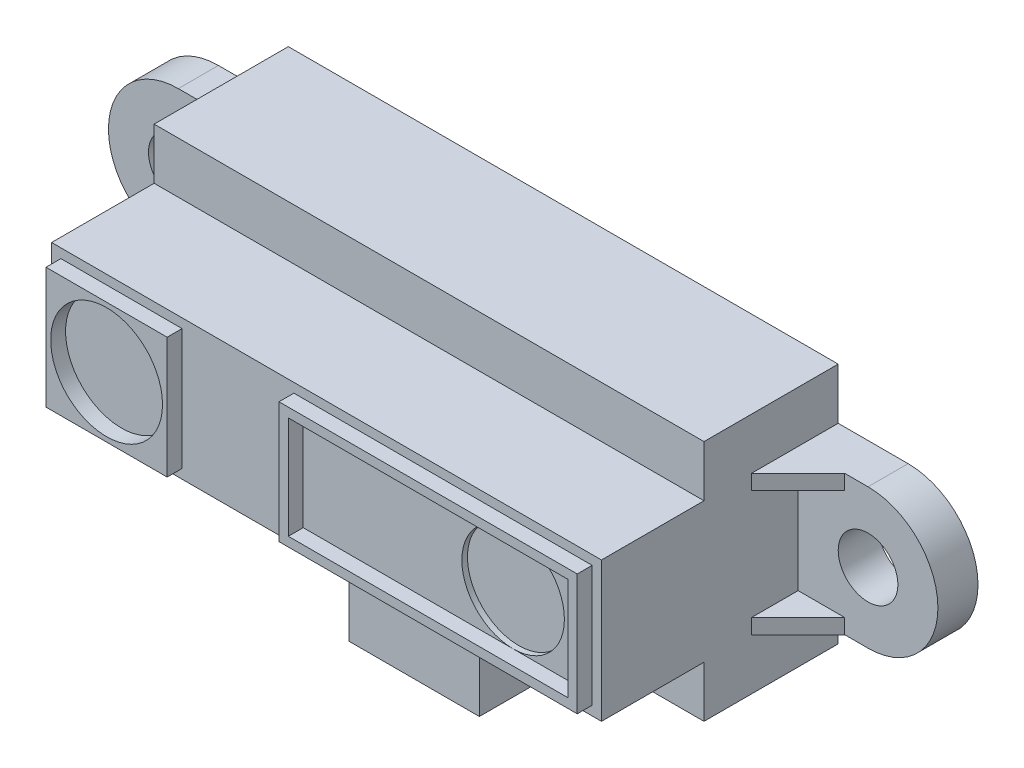
SolidWorks part; units mm, degrees
ref_plane "前视基准面" through (0, 0, 0) normal (0, 0, 1) x (1, 0, 0)
ref_plane "上视基准面" through (0, 0, 0) normal (0, 1, 0) x (1, 0, 0)
ref_plane "右视基准面" through (0, 0, 0) normal (1, 0, 0) x (0, 0, -1)
sketch "草图1" plane through (0, 0, 0) normal (0, 0, 1) x (1, 0, 0)
  line L0 (0, 0) -> (0, 16.7492) construction
  line L1 (-14.75, -3.75) -> (14.75, -3.75)
  line L2 (-14.75, -3.75) -> (-14.75, 3.75)
  line L3 (-14.75, 3.75) -> (14.75, 3.75)
  line L4 (14.75, -3.75) -> (14.75, 3.75)
  line L5 (-14.75, -3.75) -> (14.75, 3.75) construction
  line L6 (-14.75, 3.75) -> (14.75, -3.75) construction
  line L7 (-14.75, -3.75) -> (-18.5, -3.75)
  line L8 (14.75, -3.75) -> (18.5, -3.75)
  line L9 (14.75, 3.75) -> (18.5, 3.75)
  line L10 (-14.75, 3.75) -> (-18.5, 3.75)
  circle A0 centre (-18.5, 0) radius 3.75
  circle A1 centre (18.5, 0) radius 3.75
  circle A2 centre (-18.5, 0) radius 1.6
  circle A3 centre (18.5, 0) radius 1.6
  point P0 (0, 0)
  dimension "D3" = 37
  dimension "D4" = 3.2
  dimension "D5" = 3.2
  dimension "D1" = 29.5
  dimension "D2" = 7.5
extrude "凸台-拉伸1" add sketch "草图1" along normal blind 13.5 contours L1 L4 L3 L2 region at (0, 0, 0)
extrude "凸台-拉伸2" add sketch "草图1<4>" along normal blind 2.15 contours A0 A2 | A0 L2 L10 | A0 L7 L2 | L8 A1 L4 | A1 A3 | L4 A1 L9 region at (-15.5876, -2.9124, 0) region at (15.5876, -2.9124, 0) region at (-15.5876, 2.9124, 0) region at (-15.9233, -2.5767, 0) region at (15.5876, 2.9124, 0) region at (15.9233, 2.5767, 0)
sketch "草图1<4>" plane through (0, 0, 0) normal (0, 0, 1) x (1, 0, 0) same geometry as "草图1"
sketch "草图2" plane through (0, -3.75, 0) normal (0, -1, 0) x (1, 0, 0)
  line L0 (-14.75, 4.65) -> (-17.25, 2.15)
  line L1 (-14.75, 13.5) -> (-14.75, 2.15) construction
  line L2 (-14.75, 2.15) -> (-18.5, 2.15) construction
  line L3 (-17.25, 2.15) -> (-14.75, 2.15)
  line L4 (-14.75, 2.15) -> (-14.75, 4.65)
  line L6 (14.75, 13.5) -> (14.75, 2.15) construction
  line L7 (14.75, 4.65) -> (17.25, 2.15)
  line L8 (14.75, 2.15) -> (18.5, 2.15) construction
  line L9 (17.25, 2.15) -> (14.75, 2.15)
  line L10 (14.75, 2.15) -> (14.75, 4.65)
  dimension "D1" = 2.5
extrude "凸台-拉伸3" add sketch "草图2" against normal blind 0.8
sketch "草图3" plane through (0, 3.75, 0) normal (0, 1, 0) x (1, 0, 0)
  line L0 (17.25, -2.15) -> (14.75, -2.15) construction
  line L1 (14.75, -2.15) -> (14.75, -4.65) construction
  line L2 (14.75, -4.65) -> (17.25, -2.15) construction
  line L3 (-14.75, -4.65) -> (-14.75, -2.15) construction
  line L4 (-14.75, -2.15) -> (-17.25, -2.15) construction
  line L5 (-17.25, -2.15) -> (-14.75, -4.65) construction
  line L6 (17.25, -2.15) -> (14.75, -2.15)
  line L7 (14.75, -2.15) -> (14.75, -4.65)
  line L8 (14.75, -4.65) -> (17.25, -2.15)
  line L9 (-14.75, -4.65) -> (-14.75, -2.15)
  line L10 (-14.75, -2.15) -> (-17.25, -2.15)
  line L11 (-17.25, -2.15) -> (-14.75, -4.65)
extrude "凸台-拉伸4" add sketch "草图3" against normal blind 0.8
sketch "草图4" plane through (0, 0, 13.5) normal (0, 0, 1) x (1, 0, 0)
  line L0 (-14.25, 3.25) -> (-14.25, -3.25)
  line L1 (-14.75, 3.75) -> (14.75, 3.75)
  line L2 (-14.75, 3.75) -> (-14.75, -3.75)
  line L3 (-14.75, -3.75) -> (14.75, -3.75)
  line L4 (14.75, 3.75) -> (14.75, -3.75)
  line L13 (-14.25, -3.25) -> (-7.75, -3.25)
  line L14 (14.25, 3.25) -> (14.25, -3.25)
  line L15 (-14.25, 3.25) -> (-7.75, 3.25)
  line L16 (-7.75, 3.25) -> (-7.75, -3.25)
  line L17 (-1.75, -3.25) -> (14.25, -3.25)
  line L18 (-1.75, 3.25) -> (-1.75, -3.25)
  line L19 (-14.25, -3.25) -> (14.25, -3.25) construction
  line L20 (-1.75, 3.25) -> (14.25, 3.25)
  line L21 (-14.25, 3.25) -> (14.25, 3.25) construction
  line L22 (13.75, 2.75) -> (13.75, -2.75)
  line L23 (-1.25, -2.75) -> (13.75, -2.75)
  line L24 (-1.25, 2.75) -> (-1.25, -2.75)
  line L25 (-1.25, 2.75) -> (13.75, 2.75)
  circle A0 centre (-11, 0) radius 3
  point P18 (-11, 3.25)
  line M24 (-14.75, -3.75) -> (14.75, -3.75)
  line M25 (14.75, -3.75) -> (14.75, 3.75)
  line M26 (14.75, 3.75) -> (-14.75, 3.75)
  line M27 (-14.75, 3.75) -> (-14.75, -3.75)
  dimension "D4" = 6
  dimension "D1" = 0.5
  dimension "D2" = 6.5
  dimension "D3" = 16
  dimension "D5" = 0.5
extrude "切除-拉伸1" cut sketch "草图4" against normal blind 0.8 contours L15 L16 L13 L0 L18 L20 L14 L17 M27 M24 M25 M26 | L25 L24 L23 L22 | A0 region at (-2.47, 0, 13.5) region at (6.25, 0, 13.5) region at (-11, 0, 13.5)
sketch "草图7" plane through (0, 0, 0) normal (0, 0, 1) x (1, 0, 0)
  line L0 (14.75, -3.75) -> (14.75, 3.75) construction
  line L1 (-14.75, 6.5) -> (14.75, 6.5)
  line L2 (-14.75, 6.5) -> (-14.75, -6.5)
  line L3 (-14.75, -6.5) -> (14.75, -6.5)
  line L4 (14.75, 6.5) -> (14.75, -6.5)
  line L6 (-14.75, -2.95) -> (-14.75, 2.95) construction
  line L7 (0, 0) -> (-25.2709, 0) construction
  dimension "D1" = 13
extrude "凸台-拉伸5" add sketch "草图7" along normal offset from surface (7.2 mm away) 6.3 up to face at (-8, 0, 13.5)
sketch "草图10" plane through (0, -3.75, 0) normal (0, -1, 0) x (1, 0, 0)
  line L0 (-14.75, 0) -> (14.75, 0) construction
  line L1 (-5.05, 4.5) -> (5.05, 4.5)
  line L2 (-5.05, 4.5) -> (-5.05, 3.3)
  line L3 (-5.05, 3.3) -> (5.05, 3.3)
  line L4 (5.05, 4.5) -> (5.05, 3.3)
  line L5 (14.75, 0) -> (14.75, 4.65) construction
  line L7 (-3.5, 4.5) -> (3.5, 4.5)
  line L8 (-3.5, 4.5) -> (-3.5, 8)
  line L9 (-3.5, 8) -> (3.5, 8)
  line L10 (3.5, 4.5) -> (3.5, 8)
  point P6 (0, 3.3)
  point P13 (0, 8)
  line M8 (-14.75, 7.2) -> (14.75, 7.2)
  dimension "D1" = 3.3
  dimension "D2" = 10.1
  dimension "D3" = 14.75
  dimension "D4" = 1.2
  dimension "D5" = 3.5
  dimension "D6" = 7
extrude "凸台-拉伸7" add sketch "草图10" along direction (0, -1, 0) on the side of the normal offset from surface (7.75 mm away) 18 contours L4 L1 L2 L3 | L1 L10 L8 M8 | L10 L9 L8 M8 region at (0, -3.75, 3.9) region at (0, -3.75, 5.85) region at (0, -3.75, 7.6) up to face at (0, 6.5, 3.6)
sketch "草图11" plane through (0, -11.5, 0) normal (0, -1, 0) x (1, 0, 0)
  line L0 (3.5, 4.5) -> (5.05, 4.5) construction
  line L1 (-2.7976, 7.2) -> (2.7976, 7.2)
  line L2 (-2.7976, 7.2) -> (-2.7976, 4.5)
  line L3 (-2.7976, 4.5) -> (2.7976, 4.5)
  line L4 (2.7976, 7.2) -> (2.7976, 4.5)
  line L5 (3.5, 7.2) -> (3.9, 7.2)
  line L6 (3.5, 7.2) -> (3.5, 4.5)
  line L7 (3.5, 4.5) -> (3.9, 4.5)
  line L8 (3.9, 7.2) -> (3.9, 4.5)
  line L9 (-14.75, 7.2) -> (-3.5, 7.2) construction
  line L10 (-3.5074, 7.2) -> (-3.9074, 7.2)
  line L11 (-3.5074, 7.2) -> (-3.5074, 4.5)
  line L12 (-3.5074, 4.5) -> (-3.9074, 4.5)
  line L13 (-3.9074, 7.2) -> (-3.9074, 4.5)
  line L14 (-14.75, 7.2) -> (-3.5, 7.2) construction
  line L15 (-5.05, 4.5) -> (-3.5, 4.5) construction
  line L16 (3.5, 4.5) -> (5.05, 4.5) construction
  line L17 (3.5, 7.2) -> (14.75, 7.2) construction
  point P25 (0, 7.2)
  dimension "D1" = 0.4
  dimension "D2" = 0.4
extrude "切除-拉伸2" cut sketch "草图11" against normal up to surface (7.75 mm away) up to face at (0, -3.75, 8.775)
sketch "草图12" plane through (0, 0, 12.7) normal (0, 0, 1) x (1, 0, 0)
  circle A0 centre (10.0112, 0) radius 2.75
extrude "切除-拉伸3" cut sketch "草图12" against normal blind 0.3
sketch "草图13" plane through (0, 0, 0) normal (0, 0, -1) x (-1, 0, 0)
  text T0 "测距传感器\r\n0A21  10-80cm" font "汉仪长仿宋体" height 2.5
